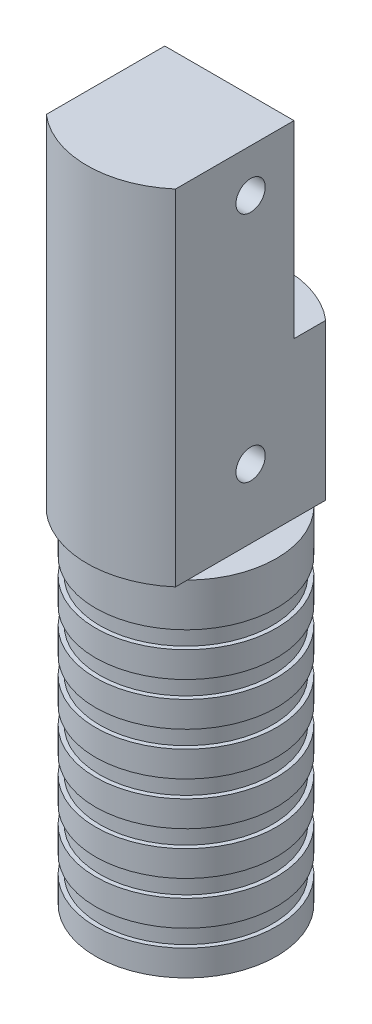
SolidWorks part; units mm, degrees
material "6061-T6 (SS)"
ref_plane "Front Plane" through (0, 0, 0) normal (0, 0, 1) x (1, 0, 0)
ref_plane "Top Plane" through (0, 0, 0) normal (0, 1, 0) x (1, 0, 0)
ref_plane "Right Plane" through (0, 0, 0) normal (1, 0, 0) x (0, 0, -1)
sketch "Sketch2" plane through (0, 0, 0) normal (0, 0, 1) x (1, 0, 0)
  line L0 (-10.5, 0) -> (10.5, 0)
  line L1 (10.5, 0) -> (10.5, -40)
  line L2 (10.5, -40) -> (-1, -40)
  line L4 (0, 0) -> (0, -40)
  line L6 (-10.5, -40) -> (-1, -40)
  line L7 (-10.5, 0) -> (-10.5, -40)
  point P4 (0, 0)
  dimension "D1" = 21
  dimension "D4" = 40
revolve "Revolve1" add sketch "Sketch2" angle 360 about L4 region at (-5.25, -20, 0)
sketch "Sketch3" plane through (0, 0, 0) normal (0, 0, 1) x (1, 0, 0)
  line L0 (-10.5, -40) -> (10.5, -40) construction
  line L1 (-10.5, -40) -> (10.5, -40)
  line L2 (10.5, -40) -> (10.5, -37)
  line L3 (10.5, -40) -> (10.5, 0) construction
  line L4 (10.5, -37) -> (10, -37)
  line L5 (10, -37) -> (10, -35)
  line L6 (10, -35) -> (10.5, -35)
  line L7 (10.5, -37) -> (10.5, -35)
  dimension "D1" = 2
  dimension "D2" = 0.5
  dimension "D3" = 3
revolve "Cut-Revolve1" cut sketch "Sketch3" angle 360 about L4
pattern_linear "LPattern1" count 7 spacing 5 along (0, 1, 0) of "Cut-Revolve1"
sketch "Sketch4" plane through (0, -40, 0) normal (0, -1, 0) x (1, 0, 0)
  point P0 (0, 0)
sketch "Sketch6" plane through (0, 0, 0) normal (0, 1, 0) x (1, 0, 0)
  line L0 (-7.5, 8.7178) -> (-7.5, -8.7178)
  line L2 (0, 0) -> (0, 11.5) construction
  line L3 (7.5, 8.7178) -> (7.5, -8.7178)
  line L4 (0, 0) -> (-7.5, 0) construction
  line L5 (-7.5, 1.5) -> (0, 1.5) construction
  arc A0 (7.5, 8.7178) -> (-7.5, 8.7178) centre (0, 0) ccw
  circle A1 centre (0, 0) radius 10.5 construction
  arc A2 (7.5, -8.7178) -> (-7.5, -8.7178) centre (0, 0) cw
  point P7 (-10.5, 0)
  dimension "D3" = 11.5
  dimension "D1" = 3
  dimension "D2" = 1.5
extrude "Boss-Extrude1" add sketch "Sketch6" along normal blind 40
hole_wizard "Ø15.0 (15) Diameter Hole1" positions "Sketch4" profile "Sketch5" hole size "Ø15.0" standard "ANSI Metric"
sketch "Sketch5" plane through (0, -40, 0) normal (1, 0, 0) x (0, 0, -1)
  line L0 (0, 0) -> (0, 34.5065)
  line L1 (0, 34.5065) -> (7.5, 30)
  line L2 (7.5, 30) -> (7.5, 0)
  line L5 (7.5, 0) -> (0, 0)
  line L10 (0, 34.5065) -> (-7.5, 30) construction
  line L11 (0, -6.35) -> (0, 107.95) construction
  dimension "Hole Dia." = 15
  dimension "Hole Depth" = 30
  dimension "Drill Angle" = 118
sketch "Sketch8" plane through (7.5, 0, 0) normal (1, 0, 0) x (0, 0, -1)
  line L2 (0, 8) -> (0, 35) construction
  line L3 (7.3485, 0) -> (-7.3485, 0) construction
  circle A0 centre (0, 8) radius 1.5 construction
  point P0 (0, 8)
  point P1 (0, 35)
  dimension "D1" = 3
  dimension "D2" = 8
  dimension "D3" = 27
hole_wizard "M3 Clearance Hole1" positions "Sketch8" profile "Sketch14" hole size "M3" standard "ANSI Metric" end condition through all
sketch "Sketch14" plane through (7.5, 8, 0) normal (0, 1, 0) x (0, 0, -1)
  line L0 (0, 0) -> (0, 18)
  line L1 (0, 18) -> (1.7, 18)
  line L2 (1.7, 18) -> (1.7, 0)
  line L5 (1.7, 0) -> (0, 0)
  line L11 (0, -6.35) -> (0, 107.95) construction
  dimension "Thru Hole Dia." = 3.4
  dimension "Thru Hole Depth" = 18
sketch "Sketch16" plane through (0, 0, 0) normal (1, 0, 0) x (0, 0, -1)
  line L0 (50.0175, 86.3497) -> (50.0175, 73.3497) construction
  line L1 (50.0175, -3.6503) -> (50.0175, 9.3497) construction
  line L2 (5.0377, 40) -> (5.0377, 18.0816)
  line L3 (5.0377, 18.0816) -> (11.5, 18.0816)
  line L4 (11.5, 40) -> (8.7178, 40) construction
  line L5 (11.5, 40) -> (8.7178, 40)
  line L6 (8.7178, 40) -> (5.0377, 40)
  line L8 (11.5, 18.0816) -> (11.5, 40)
  circle A0 centre (0, 8) radius 1.7 construction
  circle A1 centre (0, 35) radius 1.7 construction
  circle A2 centre (0, 8) radius 1.7
  circle A3 centre (0, 35) radius 1.7
  arc A4 (50.0175, -3.6503) -> (50.0175, 86.3497) centre (50.0175, 41.3497) cw construction
  arc A5 (50.0175, 73.3497) -> (50.0175, 9.3497) centre (50.0175, 41.3497) ccw construction
  dimension "D1" = 32
  dimension "D4" = 13
  dimension "D2" = 60.1162
  dimension "D3" = 50.4189
extrude "Cut-Extrude1" cut sketch "Sketch16" against normal through all both and the other way through all
